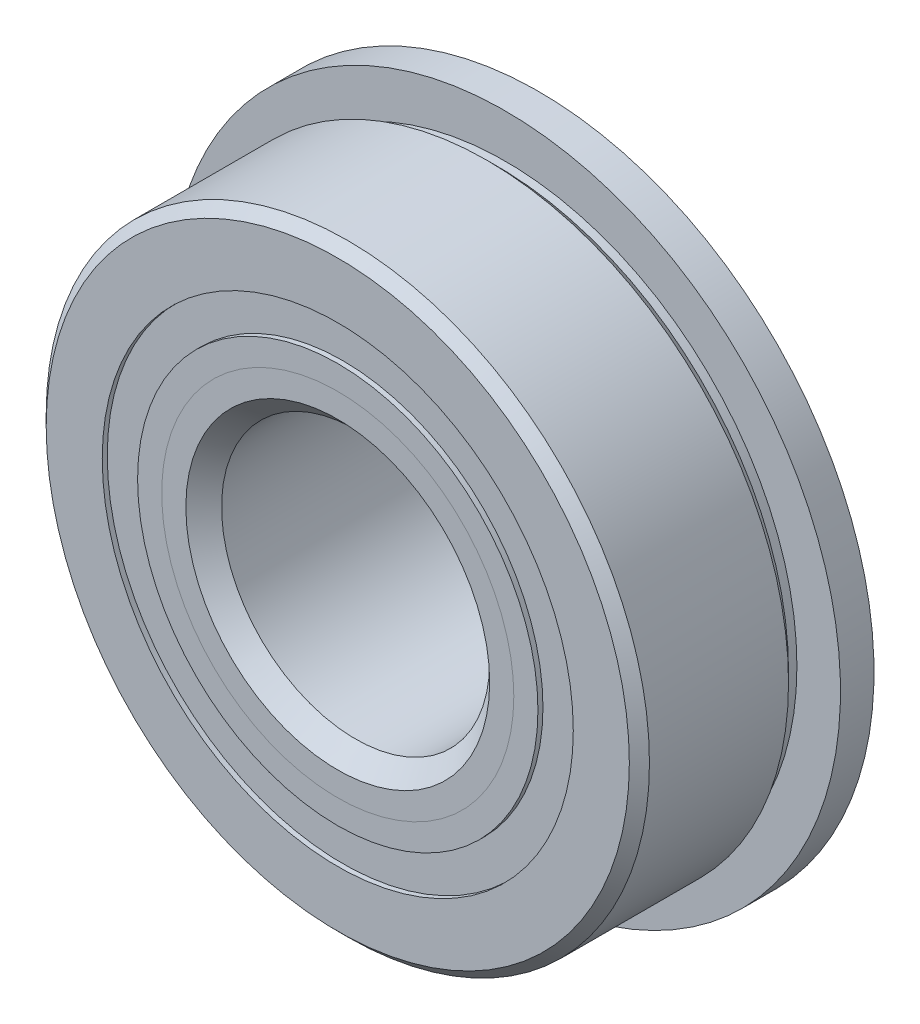
SolidWorks part; units mm, degrees
ref_plane "Front Plane" through (0, 0, 0) normal (0, 0, 1) x (1, 0, 0)
ref_plane "Top Plane" through (0, 0, 0) normal (0, 1, 0) x (1, 0, 0)
ref_plane "Right Plane" through (0, 0, 0) normal (1, 0, 0) x (0, 0, -1)
sketch "Sketch1" plane through (0, 0, 0) normal (1, 0, 0) x (0, 0, -1)
  line L0 (-4.7625, 0) -> (4.7625, 0) construction
  line L1 (0, 14.2875) -> (0, -14.2875) construction
  line L2 (4.2863, 14.2875) -> (-4.2863, 14.2875)
  line L3 (-4.2863, 14.2875) -> (-4.7625, 13.8113)
  line L4 (-4.7625, 13.8113) -> (-4.7625, 11.1561)
  line L5 (-4.7625, 11.1561) -> (-2.1167, 11.1561)
  line L6 (4.7625, 11.1561) -> (2.1167, 11.1561)
  line L7 (4.7625, 13.8113) -> (4.7625, 11.1561)
  line L8 (4.2863, 14.2875) -> (4.7625, 13.8113)
  line L9 (0, 14.2875) -> (0, 10.3187) construction
  line L10 (0, 10.3187) -> (0, 6.35) construction
  line L11 (4.7625, 0) -> (6.35, 0) construction
  arc A0 (-2.1167, 11.1561) -> (2.1167, 11.1561) centre (0, 10.3187) cw
  point P14 (0, 6.35)
  dimension "D3" = 4.2333
  dimension "D1" = 45
  dimension "Width" = 9.525
  dimension "OD" = 28.575
  dimension "D2" = 0.4763
  dimension "Shaft Dia" = 12.7
  dimension "D4" = 0.8374
  dimension "Total Wd" = 11.1125
revolve "Revolve1" add sketch "Sketch1" angle 360 about L0
sketch "Sketch2" plane through (0, 0, 0) normal (1, 0, 0) x (0, 0, -1)
  line L0 (-4.7625, 9.4814) -> (-2.1167, 9.4814)
  line L1 (-4.7625, 13.8113) -> (-4.7625, -13.8113) construction
  line L2 (-4.7625, 9.4814) -> (-4.7625, 8.3388)
  line L3 (-4.7625, 8.3388) -> (-3.6199, 7.1962)
  line L4 (-3.6199, 7.1962) -> (0, 7.1962)
  line L5 (0, 14.2875) -> (0, -14.2875) construction
  line L6 (0, 7.1962) -> (0, 8.0425)
  line L7 (0, 8.0425) -> (0, 6.35) construction
  line L8 (-4.7625, 9.4814) -> (-4.7625, 7.1962) construction
  line L9 (-4.7625, 7.1962) -> (-3.6199, 7.1962) construction
  arc A0 (-2.1167, 9.4814) -> (0, 8.0425) centre (0, 10.3187) ccw
  arc A1 (2.1167, 11.1561) -> (-2.1167, 11.1561) centre (0, 10.3187) ccw construction
  circle A2 centre (0, 10.3187) radius 2.2763 construction
  dimension "D1" = 45
revolve "Revolve2" add sketch "Sketch2" angle 360 about L0
sketch "Sketch3" plane through (0, 0, 0) normal (1, 0, 0) x (0, 0, -1)
  line L0 (-4.7625, 8.3388) -> (-3.6199, 7.1962)
  line L1 (-3.6199, 7.1962) -> (0, 7.1962)
  line L2 (0, 7.1962) -> (0, 8.0425)
  line L3 (-4.7625, 8.3388) -> (-4.7625, 7.1962)
  line L4 (-4.7625, 9.4814) -> (-4.7625, 7.1962) construction
  line L5 (-4.7625, 7.1962) -> (-3.9163, 6.35)
  line L6 (-3.9163, 6.35) -> (5.8737, 6.35)
  line L8 (5.8737, 6.35) -> (6.35, 6.8262)
  line L10 (6.35, 6.8262) -> (6.35, 9.4814)
  line L11 (6.35, 9.4814) -> (2.1167, 9.4814)
  line L13 (4.2863, 14.2875) -> (4.7625, 13.8113) construction
  circle A0 centre (0, 10.3187) radius 2.2763 construction
  arc A1 (2.1167, 9.4814) -> (0, 8.0425) centre (0, 10.3187) cw
revolve "Revolve3" add sketch "Sketch3" angle 360 about L0
sketch "Sketch5" plane through (0, 0, 0) normal (1, 0, 0) x (0, 0, -1)
  line L0 (4.7625, 13.8113) -> (4.7625, 11.1561) construction
  line L1 (4.7625, 12.4837) -> (3.175, 12.4837)
  line L2 (4.7625, 12.4837) -> (4.7625, 15.875)
  line L3 (4.7625, 15.875) -> (3.175, 15.875)
  line L4 (3.175, 12.4837) -> (3.175, 15.875)
  line L5 (6.35, 0) -> (-4.7625, 0) construction
  dimension "D1" = 1.5875
  dimension "Flange OD" = 31.75
revolve "Revolve5" add sketch "Sketch5" angle 360 about L5
sketch "Sketch6" plane through (0, 0, 0) normal (1, 0, 0) x (0, 0, -1)
  line L0 (2.3019, 14.2875) -> (2.7781, 13.8113)
  line L1 (4.2863, 14.2875) -> (-4.2863, 14.2875) construction
  line L2 (2.7781, 13.8113) -> (3.175, 13.8113)
  line L3 (3.175, 13.8113) -> (3.175, 14.2875)
  line L4 (3.175, 14.2875) -> (2.3019, 14.2875)
  line L5 (4.2863, 14.2875) -> (4.7625, 13.8113) construction
  line L6 (3.175, 12.4837) -> (3.175, 15.875) construction
  dimension "D1" = 0.3969
revolve "Cut-Revolve1" cut sketch "Sketch6" angle 360 about L0
sketch "Sketch4" plane through (0, 0, 0) normal (1, 0, 0) x (0, 0, -1)
  line L0 (-2.2763, 10.3188) -> (2.2763, 10.3188)
  circle A1 centre (0, 10.3187) radius 2.2763 construction
  arc A2 (-2.2763, 10.3188) -> (2.2763, 10.3188) centre (0, 10.3187) cw
  arc A3 (2.1167, 11.1561) -> (-2.1167, 11.1561) centre (0, 10.3187) ccw construction
revolve "Revolve4" add sketch "Sketch4" angle 360 about L0
ref_axis "Axis1" through (0, 0, -4.7625) along (0, 0, 1)
pattern_circular "CirPattern1" count 12 every 30 about axis through (0, 0, -4.7625) along (0, 0, 1) of bodies 104
sketch "Sketch7" plane through (0, 0, 0) normal (1, 0, 0) x (0, 0, -1)
  line L0 (-4.7625, 11.1561) -> (-2.1167, 11.1561) construction
  line L1 (-4.5244, 11.1561) -> (-2.2763, 11.1561)
  line L2 (-4.5244, 11.1561) -> (-4.5244, 9.4814)
  line L3 (-4.5244, 9.4814) -> (-2.2763, 9.4814)
  line L4 (-2.2763, 11.1561) -> (-2.2763, 9.4814)
  line L5 (-4.7625, 9.4814) -> (-2.1167, 9.4814) construction
  line L6 (-4.2863, 14.2875) -> (-4.7625, 13.8113) construction
  line L7 (4.7625, 11.1561) -> (2.1167, 11.1561) construction
  line L8 (4.5244, 11.1561) -> (2.2763, 11.1561)
  line L9 (4.5244, 11.1561) -> (4.5244, 9.4814)
  line L10 (4.5244, 9.4814) -> (2.2763, 9.4814)
  line L11 (2.2763, 11.1561) -> (2.2763, 9.4814)
  line L12 (6.35, 9.4814) -> (2.1167, 9.4814) construction
  line L13 (4.2863, 14.2875) -> (4.7625, 13.8113) construction
  circle A0 centre (0, 10.3187) radius 2.2763 construction
  point P10 (-4.5244, 14.0494)
  point P21 (4.5244, 14.0494)
revolve "Revolve6" add sketch "Sketch7" angle 360 about L0
equation "\"D2@Sketch1\" = \"Width@Sketch1\"*.05"
equation "\"D3@Sketch1\" = \"Width@Sketch1\"/2.25"
equation "\"D4@Sketch1\" = (((\"OD@Sketch1\"-\"Width@Sketch1\")/2)/3.25)/3.5"
equation "\"D2@CirPattern1\" = 360/\"Balls@CirPattern1\""
